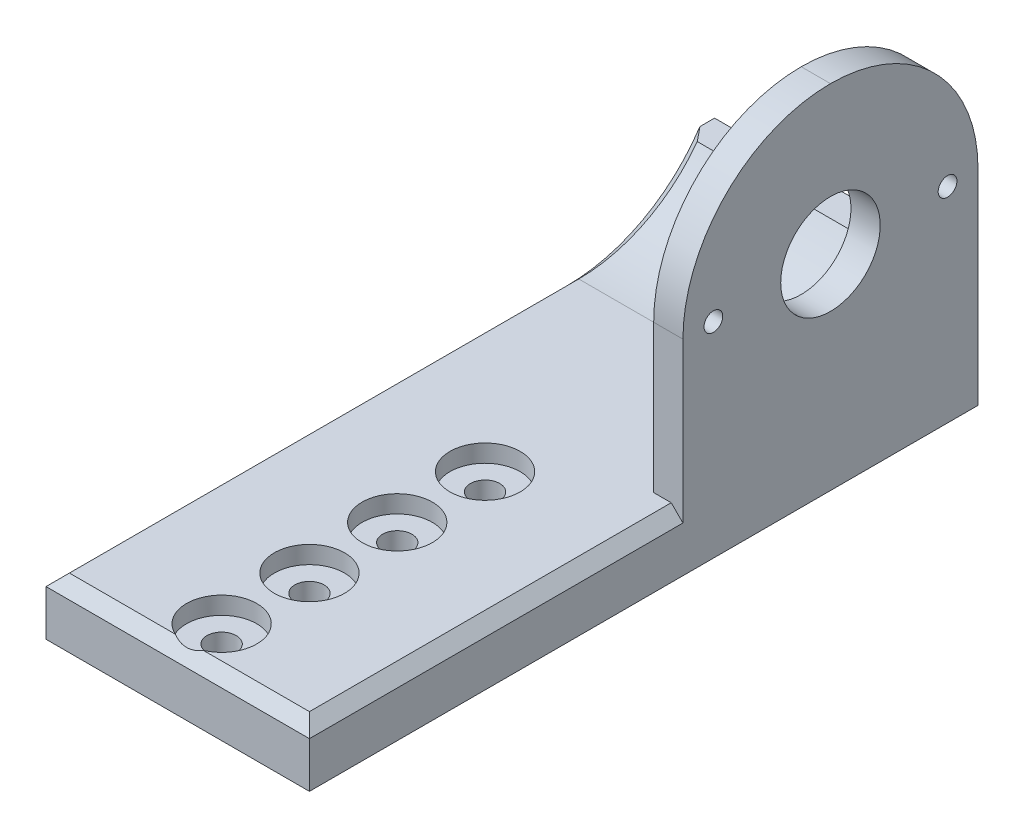
SolidWorks part; units mm, degrees
ref_plane "Front Plane" through (0, 0, 0) normal (0, 0, 1) x (1, 0, 0)
ref_plane "Top Plane" through (0, 0, 0) normal (0, 1, 0) x (1, 0, 0)
ref_plane "Right Plane" through (0, 0, 0) normal (1, 0, 0) x (0, 0, -1)
sketch "Sketch1" plane through (0, 0, 0) normal (0, 1, 0) x (1, 0, 0)
  line L1 (0, 0) -> (57.15, 0)
  line L2 (0, 0) -> (0, 145.034)
  line L3 (0, 145.034) -> (57.15, 145.034)
  line L4 (57.15, 0) -> (57.15, 145.034)
  dimension "D1" = 57.15
  dimension "D2" = 145.034
extrude "Boss-Extrude1" add sketch "Sketch1" along normal blind 25.4
sketch "Sketch3" plane through (57.15, 0, 0) normal (1, 0, 0) x (0, 0, -1)
  line L0 (0, 0) -> (145.034, 0) construction
  line L1 (145.034, 25.4) -> (145.034, 0) construction
  circle A0 centre (113.03, 44.45) radius 32.004
  dimension "D1" = 64.008
  dimension "D2" = 44.45
  dimension "D3" = 32.004
extrude "Cut-Extrude2" cut sketch "Sketch3" against normal through all
sketch "Sketch4" plane through (0, 0, 0) normal (0, -1, 0) x (-1, 0, 0)
  line L0 (0, 0) -> (-57.15, 0) construction
  line L1 (-57.15, 0) -> (-57.15, 145.034) construction
  circle A0 centre (-28.575, 9.525) radius 3.175
  circle A1 centre (-28.575, 28.575) radius 3.175
  circle A2 centre (-28.575, 47.625) radius 3.175
  circle A3 centre (-28.575, 66.675) radius 3.175
  dimension "D1" = 6.35
  dimension "D2" = 6.35
  dimension "D3" = 6.35
  dimension "D4" = 6.35
  dimension "D5" = 19.05
  dimension "D6" = 19.05
  dimension "D7" = 19.05
  dimension "D8" = 9.525
  dimension "D9" = 28.575
  dimension "D10" = 28.575
  dimension "D11" = 28.575
  dimension "D12" = 28.575
extrude "Cut-Extrude3" cut sketch "Sketch4" against normal through all
sketch "Sketch7" plane through (0, 0, 0) normal (0, -1, 0) x (1, 0, 0)
  line L0 (57.15, 0) -> (57.15, -145.034) construction
  line L1 (57.15, -81.026) -> (50.8, -81.026)
  line L2 (57.15, -81.026) -> (57.15, -145.034)
  line L3 (57.15, -145.034) -> (50.8, -145.034)
  line L4 (50.8, -81.026) -> (50.8, -145.034)
  line L8 (57.15, -145.034) -> (0, -145.034) construction
  dimension "D1" = 6.35
  dimension "D2" = 64.008
  dimension "D3" = 0
extrude "Boss-Extrude2" add sketch "Sketch7" against normal blind 76.454
fillet "Fillet1" radius 32.004 2 edges at (53.975, 76.454, -145.034) (53.975, 76.454, -81.026)
sketch "Sketch9" plane through (50.8, 0, 0) normal (-1, 0, 0) x (0, 0, 1)
  circle A1 centre (-113.03, 44.45) radius 10.795
  circle A2 centre (-138.43, 44.45) radius 2.032
  circle A3 centre (-87.63, 44.45) radius 2.032
  point P5 (-123.4328, 62.559)
  point P16 (0, 0)
  dimension "D1" = 21.59
  dimension "D4" = 4.064
  dimension "D5" = 4.064
  dimension "D2" = 25.4
  dimension "D3" = 25.4
  dimension "D6" = 32.004
  dimension "D7" = 32.004
  dimension "D8" = 32.004
  dimension "D9" = 32.004
extrude "Cut-Extrude5" cut sketch "Sketch9" against normal blind 76.454
sketch "Sketch10" plane through (0, 25.4, 0) normal (0, 1, 0) x (1, 0, 0)
  line L1 (50.8, 113.03) -> (0, 113.03)
  line L2 (50.8, 113.03) -> (50.8, 81.026)
  line L3 (50.8, 0) -> (0, 0)
  line L4 (0, 113.03) -> (0, 0)
  line L5 (57.15, 81.026) -> (50.8, 81.026)
  line L6 (57.15, 81.026) -> (57.15, 0)
  line L7 (57.15, 0) -> (50.8, 0)
extrude "Cut-Extrude7" cut sketch "Sketch10" against normal blind 12.954
sketch "Sketch11" plane through (0, 12.446, 0) normal (0, 1, 0) x (1, 0, 0)
  circle A0 centre (28.575, 66.675) radius 7.62
  circle A1 centre (28.575, 47.625) radius 7.62
  circle A2 centre (28.575, 28.575) radius 7.62
  circle A3 centre (28.575, 9.525) radius 7.62
  dimension "D1" = 15.24
  dimension "D2" = 15.24
  dimension "D3" = 15.24
  dimension "D4" = 15.24
extrude "Cut-Extrude8" cut sketch "Sketch11" against normal blind 3.81
chamfer "Chamfer1" distance 2.54 angle 45 4 edges at (0, 15.8674, -127.4276) (0, 12.446, -56.515) (28.575, 12.446, 0) (57.15, 12.446, -40.513)
